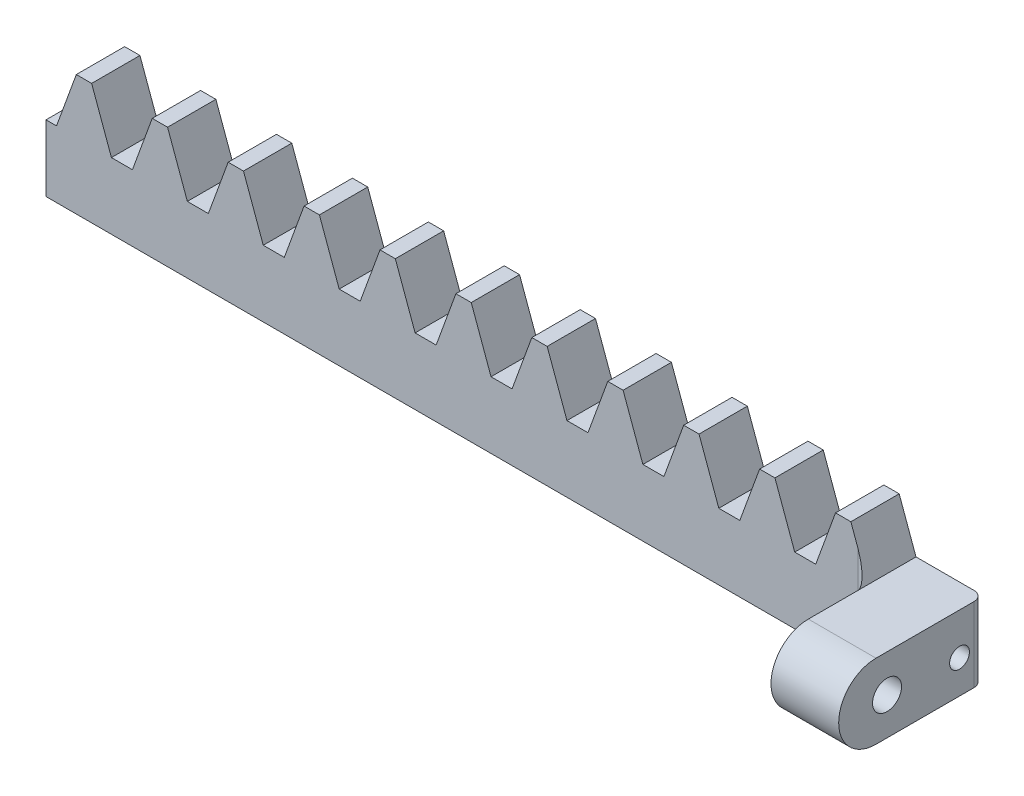
SolidWorks part; units mm, degrees
extrude "Blank" add sketch "BlankSke" against normal blind 5
sketch "BlankSke" plane through (0, 0, 0) normal (0, 0, 1) x (1, 0, 0)
  line L1 (0, 0) -> (85, 0)
  line L2 (0, 0) -> (0, 12.5)
  line L3 (0, 12.5) -> (85, 12.5)
  line L4 (85, 0) -> (85, 12.5)
  dimension "Length" = 85
ref_plane "Plane1" through (0, 0, 0) normal (0, 0, 1) x (1, 0, 0)
ref_plane "Plane2" through (0, 0, 0) normal (0, 1, 0) x (1, 0, 0)
ref_plane "Plane3" through (0, 0, 0) normal (1, 0, 0) x (0, 0, -1)
other "Configuration Table"
sketch "HoldingSke" plane through (0, 0, 0) normal (0, 1, 0) x (1, 0, 0)
  line L0 (0, 0) -> (0.0557, 0.3961)
  line L1 (-15, 0) -> (100, 0) construction
  line L2 (0, 0) -> (-2.1039, 2.3779)
  line L3 (0, 0) -> (-11.863, 4.5341)
  line L4 (0, 0) -> (8.4473, 1.7955)
  line L5 (0, 0) -> (-23.7986, -8.8762)
  line L6 (0, 0) -> (-10.5278, -7.1032)
  line L9 (-71.009, 38.7566) -> (8.8649, 67.8283)
  line L10 (-76.2, 4.8779) -> (-66.2, 4.8779)
  line L11 (0, 0) -> (-5, 0)
  line L12 (-76.2, 101.6) -> (-76.113, 101.6)
  line L13 (24.9733, 27.94) -> (52.9518, 28.4284)
  line L14 (24.9733, 27.94) -> (24.9743, 27.94)
  line L15 (24.9733, 27.94) -> (100.4006, 29.5858)
  circle A0 centre (0, 0) radius 19.05
  circle A1 centre (0, 0) radius 5
  circle A2 centre (0, 0) radius 12.7
  dimension "Num_teeth" = 12
  dimension "Width" = 5
  dimension "Length" = 85
  dimension "Pitch_height" = 10
sketch "TooCutSkeIll" plane through (0, 0, 0) normal (0, 0, 1) x (1, 0, 0)
  line L0 (-3.1105, 12.4342) -> (-1.237, 7.2869)
  line L1 (-0.6488, 6.875) -> (0.6488, 6.875)
  line L2 (1.237, 7.2869) -> (3.1105, 12.4342)
  line L3 (85, 12.5) -> (0, 12.5) construction
  line L4 (0, 0) -> (0, 64.897) construction
  line L5 (-13.208, 10) -> (12.954, 10) construction
  line L6 (0, 0) -> (85, 0) construction
  line L7 (2.2245, 10) -> (2.2245, 48.7463) construction
  line L8 (-2.2245, 10) -> (-2.2245, 48.7463) construction
  line L9 (3.2044, 12.5) -> (3.2044, 12.5254)
  line L10 (-3.2044, 12.5) -> (-3.2044, 12.5254)
  line L11 (-3.2044, 12.5254) -> (3.2044, 12.5254)
  arc A0 (0.6488, 6.875) -> (1.237, 7.2869) centre (0.6488, 7.501) ccw
  arc A1 (-1.237, 7.2869) -> (-0.6488, 6.875) centre (-0.6488, 7.501) ccw
  arc A2 (3.2044, 12.5) -> (3.1105, 12.4342) centre (3.2044, 12.4) ccw
  arc A3 (-3.1105, 12.4342) -> (-3.2044, 12.5) centre (-3.2044, 12.4) ccw
  dimension "Addendum_plus" = 2.5254
  dimension "Pitch_height" = 10
  dimension "Pressure_angle" = 20
  dimension "Gap_width" = 4.449
  dimension "Dedendum" = 3.125
extrude "ToothCutIll" [suppressed] cut sketch "TooCutSkeIll" against normal through all
sketch "TooCutSkeSim" plane through (0, 0, 0) normal (0, 0, 1) x (1, 0, 0)
  line L0 (1.0871, 6.875) -> (-1.0871, 6.875)
  line L1 (3.1437, 12.5254) -> (1.0871, 6.875)
  line L2 (0, 17.4625) -> (0, 53.467) construction
  line L3 (3.1437, 12.5254) -> (-3.1437, 12.5254)
  line L6 (-3.1437, 12.5254) -> (-1.0871, 6.875)
  line L9 (-2.2245, 10) -> (2.2245, 10) construction
  line L10 (0, 0) -> (85, 0) construction
  line L11 (2.2245, 10) -> (2.2245, 53.467) construction
  line L12 (-2.2245, 10) -> (-2.2245, 53.467) construction
  dimension "Addendum_plus" = 2.5254
  dimension "Pitch_height" = 10
  dimension "Pressure_angle" = 20
  dimension "Gap_width" = 4.449
  dimension "Dedendum" = 3.125
extrude "ToothCutSim" cut sketch "TooCutSkeSim" against normal through all
pattern_linear "TeethCuts" count 12 spacing 7.854 along (1, 0, 0) of "ToothCutIll", "ToothCutSim"
sketch "Esquisse1" plane through (0, 0, 0) normal (-1, 0, 0) x (0, 0, 1)
  line L1 (-5, 6.875) -> (-5, 0) construction
  line L2 (-5, 6.875) -> (0, 6.875) construction
  circle A0 centre (-2.5, 3.4375) radius 1.025
  dimension "D3" = 2.05
  dimension "D1" = 2.5
  dimension "D2" = 3.4375
extrude "Enlèv. mat.-Extru.1" cut sketch "Esquisse1" against normal through all
sketch "Esquisse2" plane through (0, 0, 0) normal (0, 0, 1) x (1, 0, 0)
  line L0 (85, 0) -> (85, 7.7177) construction
  line L1 (85, 0) -> (85, 7.7177)
  line L2 (85, 7.7177) -> (92, 7.7177)
  line L3 (92, 7.7177) -> (92, 0)
  line L4 (92, 0) -> (85, 0)
  dimension "D1" = 7
sketch "Esquisse3" plane through (85, 0, 0) normal (1, 0, 0) x (0, 0, -1)
  line L4 (5, 7.7177) -> (0, 7.7177)
  line L5 (0, 7.7177) -> (0, 0)
  line L6 (0, 0) -> (5, 0)
  line L7 (5, 0) -> (5, 7.7177)
  line L8 (5, 7.7177) -> (0, 7.7177)
  line L9 (0, 7.7177) -> (0, 0)
  line L10 (0, 0) -> (5, 0)
  line L11 (5, 0) -> (5, 7.7177)
  circle A0 centre (2.5, 3.4375) radius 1.025 construction
  circle A1 centre (2.5, 3.4375) radius 1.025
  dimension "D1" = 0
extrude "Boss.-Extru.1" add sketch "Esquisse3" along normal blind 7
sketch "Esquisse4" plane through (0, 0, 0) normal (0, 0, 1) x (1, 0, 0)
  line L0 (0, 0) -> (92, 0) construction
  line L1 (92, 7.7177) -> (92, 0) construction
  line L2 (92, 7.7177) -> (85, 7.7177) construction
  line L3 (85, 0) -> (92, 0)
  line L4 (92, 7.7177) -> (92, 0)
  line L5 (92, 7.7177) -> (85, 7.7177)
  line L6 (85, 7.7177) -> (85, 0)
extrude "Boss.-Extru.2" add sketch "Esquisse4" along normal blind 10
sketch "Esquisse5" plane through (85, 0, 0) normal (-1, 0, 0) x (0, 0, 1)
  line L0 (0, 7.7177) -> (10, 0) construction
  line L1 (0, 0) -> (10, 7.7177) construction
  line L4 (0, 7.7177) -> (0, 0)
  line L5 (0, 0) -> (10, 0)
  line L6 (10, 0) -> (10, 7.7177)
  line L7 (10, 7.7177) -> (0, 7.7177)
  line L9 (0, 0) -> (10, 0)
  circle A0 centre (5, 3.8588) radius 1.5
  dimension "D2" = 3
  dimension "D1" = 0
extrude "Enlèv. mat.-Extru.2" cut sketch "Esquisse5" against normal through all contours A0 region at (85, 3.8588, 5)
fillet "Congé1" 2 edges at (88.5, 7.7177, 10) (88.5, 0, 10) type full round first side face at (87.8, 7.7177, 2) second side face at (59, 0, 1.6667) middle face at (88.5, 3.8588, 10)
fillet "Congé2" radius 1 1 edges at (85, 3.8588, 0) type face fillet first side face at (85, 3.8588, 6.5) second side face at (42.2416, 9.2334, 0)
fillet "Congé3" radius 1 1 edges at (92, 3.8588, -5)
equation "' \"Module@HoldingSke\" = 6.35"
equation "' \"Num_teeth@HoldingSke\" = 12"
equation "' \"Ap@HoldingSke\" =  20"
equation "' \"Ap@HoldingSke\" = 20"
equation "' \"Width@HoldingSke\" = 0.25 * 25.4"
equation "' \"Show_teeth@HoldingSke\" = 500"
equation "' \"Backlash@HoldingSke\" = 0.009 * 25.4"
equation "' \"Addendum_fac@HoldingSke\" = 1.0"
equation "' \"Dedendum_fac@HoldingSke\" = 1.25"
equation "' \"Dedendum_add@HoldingSke\" = 0.00005 * 25.4"
equation "' \"Clearance_fac@HoldingSke\" = 0.25"
equation "' \"Pitch_height@HoldingSke\" = 1 * 25.4"
equation "' \"Length@HoldingSke\" = 4.71 * 25.4"
equation "\"Pitch@HoldingSke\" = 1 / \"Module@HoldingSke\""
equation "\"MPH@HoldingSke\" = \"Dedendum_fac@HoldingSke\" / \"Pitch@HoldingSke\" + 2 * \"Dedendum_add@HoldingSke\" + 0.002 * 25.4"
equation "\"MPH@HoldingSke\" = ((sgn( \"MPH@HoldingSke\" - \"Pitch_height@HoldingSke\")+1)*( \"MPH@HoldingSke\" - \"Pitch_height@HoldingSke\"))/2 + \"Pitch_height@HoldingSke\""
equation "\"Blank_height@BlankSke\" = \"Pitch_height@HoldingSke\" + \"Addendum_fac@HoldingSke\"  / \"Pitch@HoldingSke\" "
equation "\"Length@BlankSke\" =  \"Length@HoldingSke\""
equation "\"Face_width@Blank\" = \"Width@HoldingSke\""
equation "\"Pressure_angle@TooCutSkeIll\" = \"Ap@HoldingSke\""
equation "\"Addendum_plus@TooCutSkeIll\" =  \"Addendum_fac@HoldingSke\"  / \"Pitch@HoldingSke\" + 0.001 *25.4"
equation "\"Dedendum@TooCutSkeIll\" = \"Dedendum_fac@HoldingSke\"  / \"Pitch@HoldingSke\""
equation "\"Pitch_height@TooCutSkeIll\" =  \"MPH@HoldingSke\""
equation "\"Gap_width@TooCutSkeIll\" = 3.14159265 / 2 / \"Pitch@HoldingSke\" + 6 * \"Backlash@HoldingSke\""
equation "\"Pressure_angle@TooCutSkeSim\" = \"Ap@HoldingSke\""
equation "\"Addendum_plus@TooCutSkeSim\" =  \"Addendum_fac@HoldingSke\"  / \"Pitch@HoldingSke\" + 0.001 * 25.4"
equation "\"Dedendum@TooCutSkeSim\" = \"Dedendum_fac@HoldingSke\"  / \"Pitch@HoldingSke\""
equation "\"Pitch_height@TooCutSkeSim\" =  \"MPH@HoldingSke\""
equation "\"Gap_width@TooCutSkeSim\" = 3.14159265 / 2 / \"Pitch@HoldingSke\" + 6 * \"Backlash@HoldingSke\""
equation "\"Root_fillet@TooCutSkeIll\" = \"Clearance_fac@HoldingSke\" / \"Pitch@HoldingSke\" + \"Dedendum_add@HoldingSke\""
equation "\"Break_rad@TooCutSkeIll\" = 0.02 / \"Pitch@HoldingSke\" * 2"
equation "\"Linear_pitch@TeethCuts\" = 3.14159265 / \"Pitch@HoldingSke\""
equation "\"Num_teeth@HoldingSke\" = int( ( \"Length@HoldingSke\" + 0 ) / (3.14159265 / \"Pitch@HoldingSke\")) + 0.9999  + 1"
equation " \"Num_teeth@TeethCuts\" = int( \"Show_teeth@HoldingSke\" ) + 1"
equation " \"Num_teeth@TeethCuts\" = ((sgn( \"Num_teeth@TeethCuts\" - \"Num_teeth@HoldingSke\" )-1)*( \"Num_teeth@TeethCuts\" - \"Num_teeth@HoldingSke\" ))/-2+ \"Num_teeth@HoldingSke\""
equation " \"Num_teeth@TeethCuts\" = ((sgn( \"Num_teeth@TeethCuts\" - 2.0)+1)*( \"Num_teeth@TeethCuts\" - 2.0))/2 +2.0"
